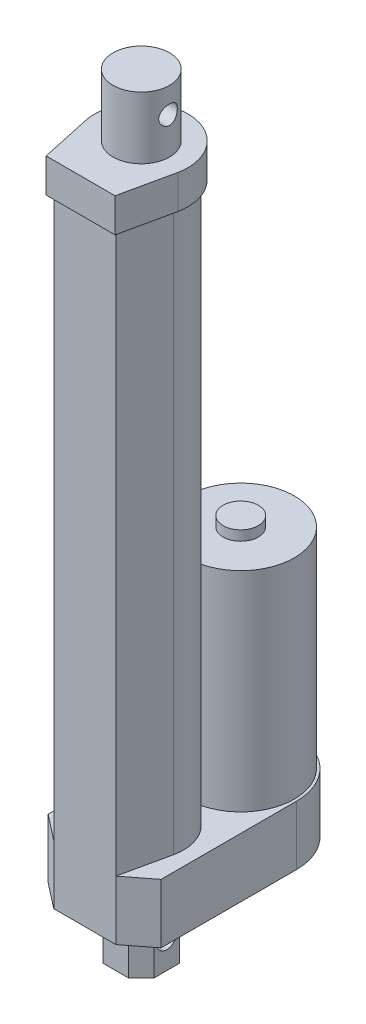
SolidWorks part; units mm, degrees
ref_plane "Piano frontale" through (0, 0, 0) normal (0, 0, 1) x (1, 0, 0)
ref_plane "Piano superiore" through (0, 0, 0) normal (0, 1, 0) x (1, 0, 0)
ref_plane "Piano destro" through (0, 0, 0) normal (1, 0, 0) x (0, 0, -1)
sketch "Schizzo1" plane through (0, 0, 0) normal (0, 1, 0) x (1, 0, 0)
  line L0 (-11, 0) -> (11, 0)
  line L1 (11, 0) -> (20, 7)
  line L2 (20, 7) -> (20, 55)
  line L3 (-20, 55) -> (-20, 7)
  line L4 (-20, 7) -> (-11, 0)
  line L5 (-20, 7) -> (20, 7) construction
  line L6 (0, 0) -> (0, 11) construction
  line L7 (9, 11) -> (-9, 11) construction
  line L8 (9, 11) -> (9, 29) construction
  line L9 (9, 29) -> (-9, 29) construction
  line L10 (-9, 11) -> (-9, 29) construction
  line L11 (4.5, 11) -> (-4.5, 11)
  line L12 (-4.5, 11) -> (-9, 15.5)
  line L13 (-9, 15.5) -> (-9, 24.5)
  line L14 (-9, 24.5) -> (-4.5, 29)
  line L15 (-4.5, 29) -> (4.5, 29)
  line L16 (4.5, 29) -> (9, 24.5)
  line L17 (9, 24.5) -> (9, 15.5)
  line L18 (9, 15.5) -> (4.5, 11)
  arc A0 (20, 55) -> (-20, 55) centre (0, 55) ccw
  point P7 (0, 0)
  point P17 (0, 29)
  point P24 (0, 29)
  dimension "D4" = 75
  dimension "D1" = 7
  dimension "D2" = 9
  dimension "D3" = 22
  dimension "D5" = 18
  dimension "D6" = 9
  dimension "D7" = 11
extrude "Estrusione-Estrusione1" add sketch "Schizzo1" along normal blind 21 contours L18 L17 L16 L15 L14 L13 L12 L11 | L2 A0 L3 L4 L0 L1 L17 L18 L11 L12 L13 L14 L15 L16 region at (0, 0, -38.1067) region at (0, 0, -20)
extrude "Estrusione-Estrusione2" add sketch "Schizzo1<3>" against normal blind 19 contours L18 L17 L16 L15 L14 L13 L12 L11 region at (0, 0, -20)
sketch "Schizzo1<3>" plane through (0, 0, 0) normal (0, 1, 0) x (1, 0, 0) same geometry as "Schizzo1"
hole_wizard "Foro per Vite M6.5-1" positions "Schizzo2" profile "Schizzo4" hole size "M6.5" standard "ISO"
sketch "Schizzo2" plane through (9, 0, 0) normal (1, 0, 0) x (0, 0, -1)
  line L0 (20, -9) -> (20, 0) construction
  line L1 (24.5, 0) -> (15.5, 0) construction
  point P1 (20, -9)
  dimension "D1" = 9
sketch "Schizzo4" plane through (9, -9, -20) normal (0, 1, 0) x (0, 0, -1)
  line L0 (0, 0) -> (0, 82.1331)
  line L1 (0, 82.1331) -> (3.55, 80)
  line L2 (3.55, 80) -> (3.55, 0)
  line L5 (3.55, 0) -> (0, 0)
  line L10 (0, 82.1331) -> (-3.55, 80) construction
  line L11 (0, -6.35) -> (0, 107.95) construction
  dimension "Hole Dia." = 7.1
  dimension "Hole Depth" = 80
  dimension "Drill Angle" = 118
sketch "Schizzo5" plane through (0, 21, 0) normal (0, 1, 0) x (1, 0, 0)
  line L0 (0, 55.2) -> (0, 0) construction
  circle A0 centre (0, 55.2) radius 19
  arc A1 (20, 55) -> (-20, 55) centre (0, 55) ccw construction
  dimension "D1" = 38
  dimension "D2" = 0.2
extrude "Estrusione-Estrusione3" add sketch "Schizzo5" along normal blind 74
sketch "Schizzo7" plane through (0, 95, 0) normal (0, 1, 0) x (1, 0, 0)
  circle A0 centre (0, 55.2) radius 6.25
  dimension "D1" = 12.5
extrude "Estrusione-Estrusione4" add sketch "Schizzo7" along normal blind 3.5
sketch "Schizzo8" plane through (0, 21, 0) normal (0, 1, 0) x (1, 0, 0)
  line L0 (-11, 0) -> (11, 0)
  line L1 (11, 0) -> (14.6572, 16.8115)
  line L2 (-14.6572, 16.8115) -> (-11, 0)
  line L3 (0, 20) -> (0, 0) construction
  arc A0 (14.6572, 16.8115) -> (-14.6572, 16.8115) centre (0, 20) ccw
  dimension "D1" = 15
  dimension "D2" = 20
extrude "Estrusione-Estrusione5" add sketch "Schizzo8" along normal blind 198
sketch "Schizzo9" plane through (0, 219, 0) normal (0, 1, 0) x (1, 0, 0)
  line L0 (-12.2088, -1.5) -> (12.2088, -1.5)
  line L1 (12.2088, -1.5) -> (16.1923, 16.8115)
  line L2 (-12.2088, -1.5) -> (-16.1923, 16.8115)
  line L5 (11, 0) -> (14.6572, 16.8115) construction
  line L6 (-16.1923, 16.8115) -> (16.1923, 16.8115) construction
  line L7 (0, 0) -> (0, 16.8115) construction
  line L8 (-11, 0) -> (11, 0) construction
  line L10 (-14.6572, 16.8115) -> (-11, 0) construction
  line L11 (-14.6572, 16.8115) -> (-11, 0) construction
  arc A0 (16.1923, 16.8115) -> (-16.1923, 16.8115) centre (0, 20) ccw
  dimension "D1" = 1.5
  dimension "D2" = 1.5
extrude "Estrusione-Estrusione6" add sketch "Schizzo9" along normal blind 12
sketch "Schizzo10" plane through (0, 231, 0) normal (0, 1, 0) x (1, 0, 0)
  circle A0 centre (0, 20) radius 10
  dimension "D1" = 20
extrude "Estrusione-Estrusione7" add sketch "Schizzo10" along normal blind 22
hole_wizard "Foro per Vite M6-1" positions "Schizzo3D1" profile "Schizzo11" hole size "M6" standard "ISO"
sketch3d "Schizzo3D1"
  line L0 (10, 244, -20) -> (0, 244, -20) construction
  circle A1 centre (0, 253, -20) radius 10 construction
  point P0 (10, 244, -20)
  point P14 (0, 263, -20)
  dimension "D1" = 9
sketch "Schizzo11" plane through (10, 244, -20) normal (0, 1, 0) x (0, 0, -1)
  line L0 (0, 0) -> (0, 81.9828)
  line L1 (0, 81.9828) -> (3.3, 80)
  line L2 (3.3, 80) -> (3.3, 0)
  line L5 (3.3, 0) -> (0, 0)
  line L10 (0, 81.9828) -> (-3.3, 80) construction
  line L11 (0, -6.35) -> (0, 107.95) construction
  dimension "Hole Dia." = 6.6
  dimension "Hole Depth" = 80
  dimension "Drill Angle" = 118
